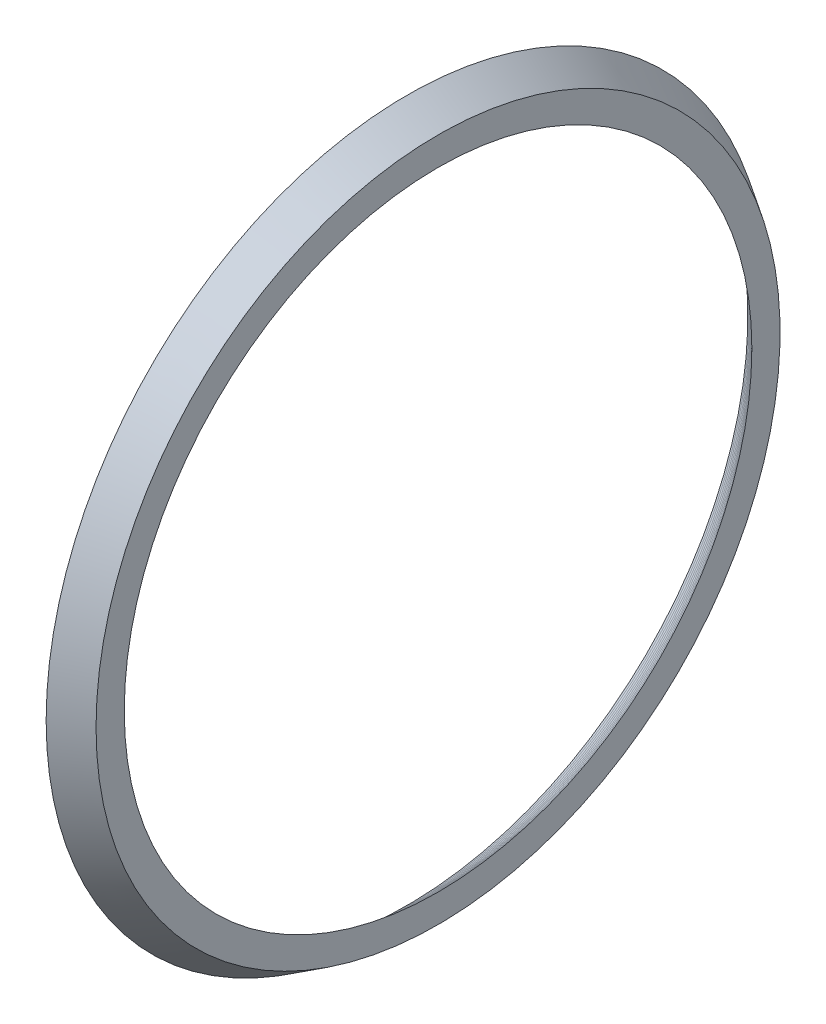
SolidWorks part; units mm, degrees
ref_plane "Front Plane" through (0, 0, 0) normal (0, 0, 1) x (1, 0, 0)
ref_plane "Top Plane" through (0, 0, 0) normal (0, 1, 0) x (1, 0, 0)
ref_plane "Right Plane" through (0, 0, 0) normal (1, 0, 0) x (0, 0, -1)
sketch "Bottle_Liner_Top Sketch" plane through (0, 0, 0) normal (0, 0, 1) x (1, 0, 0)
  line L0 (-300, 0) -> (300, 0) construction
  line L1 (3.175, 64.6949) -> (2.3812, 65.4939)
  line L2 (2.3812, 65.4939) -> (1.5875, 66.2603)
  line L3 (1.5875, 66.2603) -> (0.7938, 66.9953)
  line L4 (0.7938, 66.9953) -> (0, 67.7)
  line L5 (0, 67.7) -> (-0.7938, 68.3752)
  line L6 (-0.7938, 68.3752) -> (-1.5875, 69.0219)
  line L7 (-1.5875, 69.0219) -> (-2.3812, 69.6408)
  line L8 (-2.3812, 69.6408) -> (-3.175, 70.2326)
  line L9 (-3.175, 70.2326) -> (-3.175, 74.4485)
  line L10 (-3.175, 74.4485) -> (3.175, 70.5115)
  line L11 (3.175, 70.5115) -> (3.175, 64.6949)
revolve "Bottle_Liner_Top" add sketch "Bottle_Liner_Top Sketch" angle 360 about L0
ref_axis "Engine Axis" through (3.4925, 0, 0) along (-1, 0, 0)
